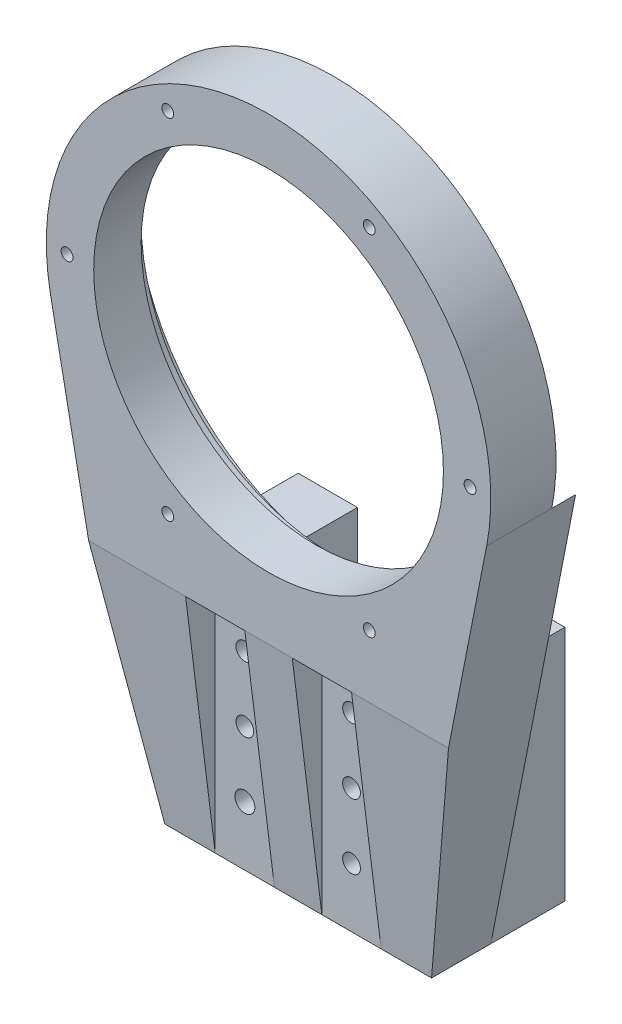
SolidWorks part; units mm, degrees
material "ABS"
ref_plane "Front Plane" through (0, 0, 0) normal (0, 0, 1) x (1, 0, 0)
ref_plane "Top Plane" through (0, 0, 0) normal (0, 1, 0) x (1, 0, 0)
ref_plane "Right Plane" through (0, 0, 0) normal (1, 0, 0) x (0, 0, -1)
sketch "Sketch1" plane through (0, 0, 0) normal (0, 0, 1) x (1, 0, 0)
  line L0 (0, 0) -> (0, -75.7544) construction
  line L1 (-22.5, -80) -> (22.5, -80)
  line L4 (22.5, -80) -> (36.7966, -7.2291)
  line L5 (-22.5, -80) -> (-36.7966, -7.2291)
  line L6 (-36.7966, -7.2291) -> (0, 0) construction
  line L7 (0, 0) -> (36.7966, -7.2291) construction
  circle A0 centre (0, 0) radius 29.5
  circle A1 centre (0, 0) radius 37.5
  arc A2 (-36.7966, -7.2291) -> (36.7966, -7.2291) centre (0, 0) ccw
  dimension "D1" = 45
  dimension "D2" = 75
  dimension "D3" = 59
  dimension "D4" = 80
  dimension "D6" = 22.5
extrude "Boss-Extrude1" add sketch "Sketch1" along normal blind 15 contours A0 A2 A1 | A1 L1 A2 region at (0, -53.8261, 0) region at (-3.5289, 36.2681, 0)
sketch "Sketch2" plane through (0, 0, 0) normal (0, 0, -1) x (-1, 0, 0)
  circle A0 centre (0, 0) radius 32.5
  circle A1 centre (0, 0) radius 27.5
extrude "Cut-Extrude1" cut sketch "Sketch2" against normal blind 7
sketch "Sketch9" plane through (0, 0, 15) normal (0, 0, 1) x (1, 0, 0)
  line L0 (60.1553, 0) -> (-60.1553, 0) construction
  line L1 (-60.1553, 0) -> (0, 0) construction
  line L2 (0, 0) -> (27.4803, 47.5973) construction
  line L3 (27.4803, 47.5973) -> (-28.626, -49.5817) construction
  line L4 (-28.626, -49.5817) -> (0, 0) construction
  line L5 (-29.2217, 50.6135) -> (0, 0) construction
  line L6 (0, 0) -> (29.2328, -50.6327) construction
  circle A0 centre (0, 0) radius 34 construction
  circle A1 centre (17, 29.4449) radius 1
  circle A2 centre (34, 0) radius 1
  circle A3 centre (17, -29.4449) radius 1
  circle A4 centre (-17, -29.4449) radius 1
  circle A5 centre (-34, 0) radius 1
  circle A6 centre (-17, 29.4449) radius 1
  dimension "D1" = 60
  dimension "D2" = 60
extrude "Cut-Extrude5" cut sketch "Sketch9" against normal blind 15
sketch "Sketch10" plane through (0, 0, 0) normal (0, 0, -1) x (-1, 0, 0)
  circle A0 centre (0, 0) radius 37.5
extrude "Cut-Extrude6" cut sketch "Sketch10" against normal blind 4
sketch "Sketch11" plane through (0, 0, 0) normal (1, 0, 0) x (0, 0, -1)
  line L4 (-15, -80) -> (-15, -40)
  line L5 (-15, -80) -> (-15, -7.2291) construction
  line L9 (-15, -40) -> (-10, -80)
  line L10 (-15, -80) -> (0, -80) construction
  line L11 (-10, -80) -> (-15, -80)
  dimension "D1" = 5
  dimension "D2" = 40
extrude "Cut-Extrude7" cut sketch "Sketch11" against normal blind 35 and the other way blind 35
sketch "Sketch12" plane through (0, 0, 15) normal (0, 0, 1) x (1, 0, 0)
  line L0 (22.5, -80) -> (-22.5, -80) construction
  line L1 (-14, -80) -> (-4, -80)
  line L2 (-14, -80) -> (-14, -40)
  line L3 (-14, -40) -> (-4, -40)
  line L4 (-4, -80) -> (-4, -40)
  line L5 (-30.3584, -40) -> (30.3584, -40) construction
  line L6 (0, 0) -> (0, -92.2976) construction
  line L7 (4, -80) -> (14, -80)
  line L8 (4, -80) -> (4, -40)
  line L9 (4, -40) -> (14, -40)
  line L10 (14, -80) -> (14, -40)
  dimension "D1" = 10
  dimension "D2" = 10
  dimension "D3" = 4
  dimension "D4" = 4
extrude "Cut-Extrude8" cut sketch "Sketch12" against normal blind 5
sketch "Sketch13" plane through (0, 0, 10) normal (0, 0, 1) x (1, 0, 0)
  line L0 (0, 0) -> (0, -103.8818) construction
  line L2 (-14, -80) -> (-4, -80) construction
  line L3 (4, -80) -> (14, -80) construction
  circle A0 centre (-9, -48) radius 1.5
  circle A1 centre (-9, -59) radius 1.5
  circle A2 centre (-9, -70) radius 1.6822
  circle A3 centre (9, -70) radius 1.5
  circle A4 centre (9, -59) radius 1.5
  circle A5 centre (9, -48) radius 1.5
  dimension "D1" = 9
  dimension "D2" = 9
  dimension "D3" = 9
  dimension "D4" = 9
  dimension "D5" = 9
  dimension "D6" = 9
  dimension "D7" = 10
  dimension "D8" = 10
  dimension "D9" = 11
  dimension "D10" = 11
  dimension "D11" = 11
  dimension "D12" = 11
extrude "Cut-Extrude9" cut sketch "Sketch13" against normal blind 10
sketch "Sketch14" plane through (0, 0, 0) normal (0, 0, -1) x (-1, 0, 0)
  line L0 (-12.5, -80) -> (-12.5, -40)
  line L1 (22.5, -80) -> (-22.5, -80) construction
  line L2 (-12.5, -80) -> (-22.5, -80)
  line L5 (22.5, -80) -> (12.5, -80)
  line L6 (12.5, -80) -> (12.5, -40)
  line L10 (-22.5, -80) -> (-22.5, -40)
  line L11 (-22.5, -40) -> (-12.5, -40)
  line L12 (22.5, -80) -> (22.5, -40)
  line L13 (22.5, -40) -> (12.5, -40)
  dimension "D1" = 40
  dimension "D2" = 10
  dimension "D3" = 10
  dimension "D4" = 40
extrude "Boss-Extrude2" add sketch "Sketch14" along normal blind 12.5
